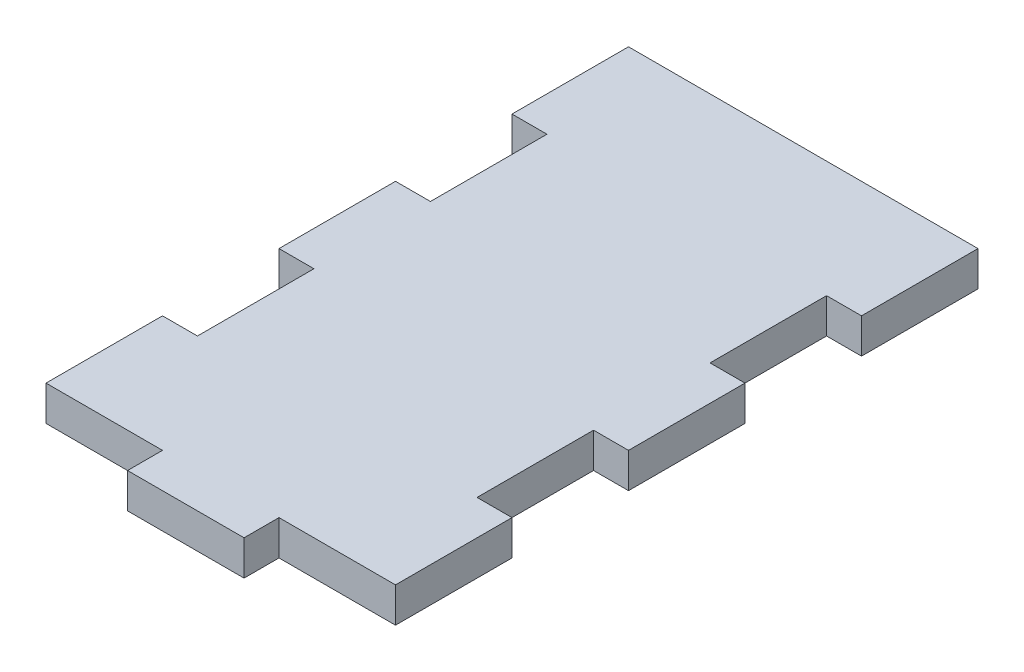
SolidWorks part; units mm, degrees
ref_plane "Alzado" through (0, 0, 0) normal (0, 0, 1) x (1, 0, 0)
ref_plane "Planta" through (0, 0, 0) normal (0, 1, 0) x (1, 0, 0)
ref_plane "Vista lateral" through (0, 0, 0) normal (1, 0, 0) x (0, 0, -1)
sketch "Croquis1" plane through (0, 0, 0) normal (0, 1, 0) x (1, 0, 0)
  line L0 (0, 0) -> (10, 0)
  line L1 (0, 0) -> (0, 10)
  line L2 (0, 50) -> (30, 50)
  line L3 (30, 50) -> (30, 40)
  line L5 (20, -3) -> (10, -3)
  line L6 (10, -3) -> (10, 0)
  line L7 (0, 25) -> (0, 30)
  line L8 (0, 30) -> (3, 30)
  line L9 (3, 30) -> (3, 40)
  line L10 (3, 40) -> (0, 40)
  line L11 (0, 40) -> (0, 50)
  line L12 (3, 10) -> (0, 10)
  line L13 (3, 20) -> (3, 10)
  line L14 (0, 20) -> (3, 20)
  line L15 (20, -3) -> (20, 0)
  line L16 (30, 20) -> (27, 20)
  line L17 (27, 20) -> (27, 10)
  line L18 (27, 10) -> (30, 10)
  line L19 (0, 20) -> (0, 30)
  line L20 (27, 40) -> (30, 40)
  line L21 (27, 30) -> (27, 40)
  line L22 (30, 30) -> (27, 30)
  line L23 (30, 10) -> (30, 0)
  line L24 (30, 30) -> (30, 20)
  line L25 (20, 0) -> (30, 0)
  dimension "D1" = 30
  dimension "D2" = 50
  dimension "D5" = 5
  dimension "D6" = 3
  dimension "D7" = 10
extrude "Saliente-Extruir1" add sketch "Croquis1" along normal blind 3 contours L15 L25 L23 L18 L17 L16 L24 L22 L21 L20 L3 L2 L11 L10 L9 L8 L7 L19 L14 L13 L12 L1 L0 L6 L5 region at (15, 0, -24.4362)
